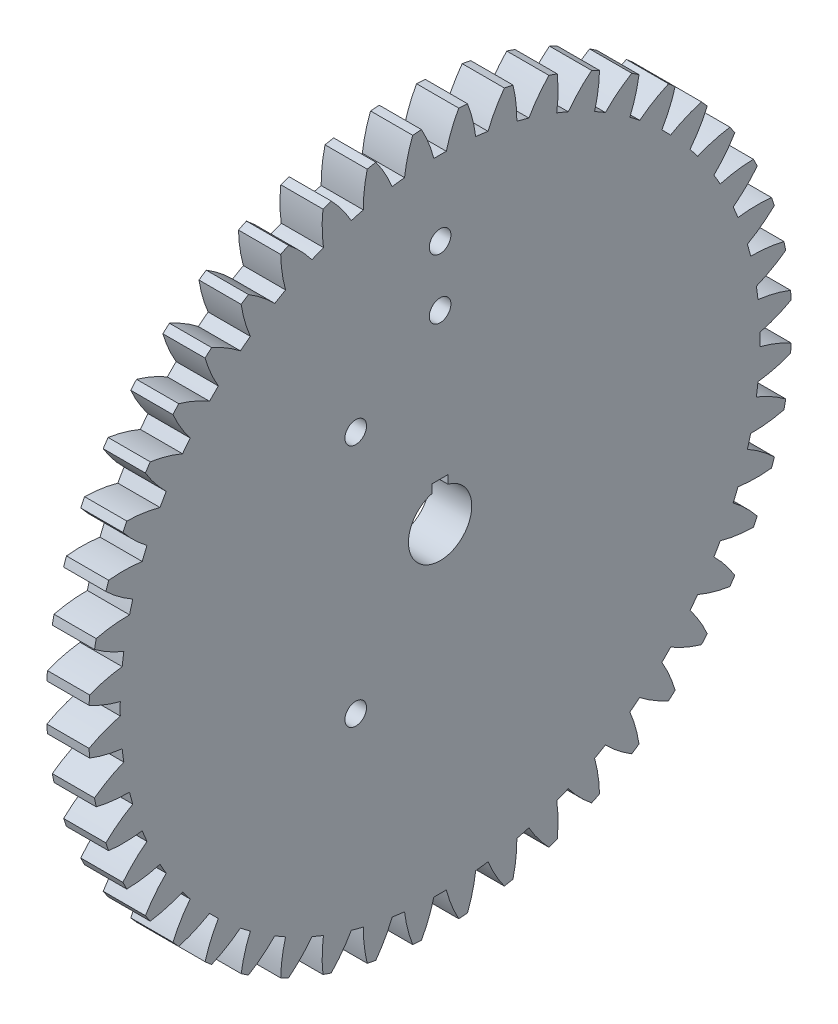
SolidWorks part; units mm, degrees
ref_plane "Plane1" through (0, 0, 0) normal (0, 0, 1) x (1, 0, 0)
ref_plane "Plane2" through (0, 0, 0) normal (0, 1, 0) x (1, 0, 0)
ref_plane "Plane3" through (0, 0, 0) normal (1, 0, 0) x (0, 0, -1)
other "Configuration Table"
sketch "HoldingSke" plane through (0, 0, 0) normal (0, 1, 0) x (1, 0, 0)
  line L0 (0, 0) -> (101.9755, -113.2553)
  line L1 (-15, 0) -> (100, 0) construction
  line L2 (0, 0) -> (-2.1039, 2.3779)
  line L3 (0, 0) -> (-11.863, 4.5341)
  line L4 (0, 0) -> (5.7786, 6.4178)
  line L5 (0, 0) -> (-47.5972, -17.7524)
  line L6 (0, 0) -> (-10.5278, -7.1032)
  line L7 (-2.1039, 2.3779) -> (8.8308, 51.9872)
  line L8 (-76.2, 54.61) -> (-54.9402, 54.61)
  line L9 (-71.009, 38.7566) -> (-53.1078, 45.2721)
  line L10 (-76.2, 71.12) -> (104.1128, 71.12)
  line L11 (0, 0) -> (-12.7, 0)
  line L12 (-76.2, 101.6) -> (-76.0298, 101.6)
  line L13 (24.9733, 27.94) -> (52.9518, 28.4284)
  line L14 (24.9733, 27.94) -> (24.9746, 27.94)
  line L15 (24.9733, 27.94) -> (100.4006, 29.5858)
  circle A0 centre (0, 0) radius 9.525
  circle A1 centre (0, 0) radius 38.1
  circle A2 centre (0, 0) radius 38.1
  circle A3 centre (0, 0) radius 9.525
  dimension "Num_teeth" = 48
  dimension "H" = 19.05
  dimension "Pitch_radius" = 180.3128
  dimension "Width" = 12.7
  dimension "Thickness" = 12.7
sketch "BasProSke" plane through (0, 0, 0) normal (0, 1, 0) x (1, 0, 0)
  line L0 (-10, 0) -> (60, 0) construction
  line L1 (0, 0) -> (0, 105.8333)
  line L2 (0, 0) -> (12.7, 0)
  line L3 (12.7, 0) -> (12.7, 105.8333)
  line L4 (12.7, 105.8333) -> (0, 105.8333)
  dimension "Thickness" = 12.7
  dimension "Diameter" = 211.6667
revolve "Base-Revolve" add sketch "BasProSke" angle 360 about L0
sketch "TooCutSke" plane through (0, 0, 0) normal (1, 0, 0) x (0, 0, -1)
  line L1 (0, 0) -> (0, 107) construction
  line L2 (0, 0) -> (-3.622, 101.5354) construction
  line L3 (0, 0) -> (-13.284, 202.675) construction
  line L4 (-3.622, 101.5354) -> (-6.642, 101.3375) construction
  arc A0 (1.8768, 96.2888) -> (-1.8768, 96.2888) centre (0, 0) ccw
  arc A1 (5.6186, 105.7095) -> (-5.6186, 105.7095) centre (0, 0) ccw
  circle A2 centre (0, 0) radius 101.6 construction
  circle A3 centre (0, 0) radius 95.4728 construction
  arc A4 (-1.8768, 96.2888) -> (-5.6186, 105.7095) centre (-41.2227, 86.1147) ccw
  arc A5 (5.6186, 105.7095) -> (1.8768, 96.2888) centre (41.2227, 86.1147) ccw
extrude "ToothCut" cut sketch "TooCutSke" along normal through all
fillet "Breaks" [suppressed] radius 0.0847 tangent propagation no
fillet "RootFillets" [suppressed] radius 1.0596
pattern_circular "TeethCuts" count 48 every 7.5 about axis through (-10, 0, 0) along (1, 0, 0) of "ToothCut", "RootFillets", "Breaks"
sketch "HubNeaOneSke" plane through (0, 0, 0) normal (-1, 0, 0) x (0, 0, 1)
  circle A0 centre (0, 0) radius 38.1
  dimension "Diameter" = 76.2
extrude "HubNearOne" [suppressed] add sketch "HubNeaOneSke" along normal blind 38.1001
sketch "HubNeaBotSke" plane through (0, 0, 0) normal (-1, 0, 0) x (0, 0, 1)
  circle A0 centre (0, 0) radius 38.1
  dimension "Diameter" = 76.2
extrude "HubNearBoth" [suppressed] add sketch "HubNeaBotSke" along normal blind 19.0501
ref_plane "FarPln" through (12.7, 0, 0) normal (1, 0, 0) x (0, 0, -1)
sketch "HubFarSke" plane through (12.7, 0, 0) normal (1, 0, 0) x (0, 0, -1)
  circle A0 centre (0, 0) radius 38.1
  dimension "Diameter" = 76.2
extrude "HubFar" [suppressed] add sketch "HubFarSke" along normal blind 19.0501
sketch "BorSke" plane through (0, 0, 0) normal (1, 0, 0) x (0, 0, -1)
  circle A0 centre (0, 0) radius 9.525
  dimension "Diameter" = 19.05
extrude "Bore" cut sketch "BorSke" along normal mid plane 101.6002
sketch "KeySke" plane through (0, 0, 0) normal (1, 0, 0) x (0, 0, -1)
  line L0 (-2.3813, 0) -> (-2.3813, 11.7348)
  line L1 (-2.3813, 11.7348) -> (2.3813, 11.7348)
  line L2 (2.3813, 11.7348) -> (2.3813, 0)
  line L3 (0, 0) -> (0, 34) construction
  line L4 (-2.3813, 0) -> (2.3813, 0)
  dimension "Width" = 4.7625
extrude "Keyway" cut sketch "KeySke" along normal mid plane 101.6002
pattern_circular "Keyway2" [suppressed] count 2 every 90 about axis through (-10, 0, 0) along (1, 0, 0)
sketch "Sketch1" plane through (0, 0, 0) normal (-1, 0, 0) x (0, 0, 1)
  line L0 (-32.7257, 64.77) -> (54.9532, 64.77) construction
  circle A0 centre (0, 73.7743) radius 3.2512
  circle A1 centre (0, 55.7657) radius 3.2512
  dimension "D1" = 6.5024
  dimension "D2" = 18.0086
  dimension "D3" = 64.77
extrude "Cut-Extrude1" cut sketch "Sketch1" against normal through all
sketch "Sketch2" plane through (0, 0, 0) normal (-1, 0, 0) x (0, 0, 1)
  line L0 (41.1124, 0) -> (-29.3128, 0) construction
  circle A0 centre (25.4, -36.703) radius 3.2512
  circle A1 centre (25.4, 36.703) radius 3.2512
  dimension "D2" = 6.5024
  dimension "D1" = 73.406
  dimension "D3" = 25.4
extrude "Cut-Extrude2" cut sketch "Sketch2" against normal through all
equation "' \"Pitch@HoldingSke\" = 4"
equation "' \"Num_teeth@HoldingSke\" = 12"
equation "' \"Ap@HoldingSke\" =  20"
equation "' \"Ap@HoldingSke\" = 20"
equation "' \"Width@HoldingSke\" = 0.5"
equation "' \"Hub_dia@HoldingSke\"= 1"
equation "' \"Hub_dia@HoldingSke\" = 1"
equation "' \"Overall_len@HoldingSke\" = 1.0"
equation "' \"Bore@HoldingSke\" = 0.75"
equation "' \"T_dim@HoldingSke\" = 0.85"
equation "' \"Width@KeySke\" = 0.25"
equation "' \"Show_teeth@HoldingSke\" = 13"
equation "' \"Backlash@HoldingSke\" = 0.009"
equation "' \"Addendum_fac@HoldingSke\" = 1.0"
equation "' \"Dedendum_fac@HoldingSke\" = 1.25"
equation "' \"Dedendum_add@HoldingSke\" = 0.00005"
equation "' \"Clearance_fac@HoldingSke\" = 0.25"
equation "' \"Pitch@HoldingSke\" = 0.5"
equation "' \"Num_teeth@HoldingSke\" = 23"
equation "' \"Show_teeth@HoldingSke\" = 23"
equation "' \"Backlash@HoldingSke\" = 0.0375"
equation "\"Overcut_dia@TooCutSke\" = (\"Num_teeth@HoldingSke\" + 2 * \"Addendum_fac@HoldingSke\") / \"Pitch@HoldingSke\" + 0.002"
equation "\"Pitch_dia@TooCutSke\" = \"Num_teeth@HoldingSke\" / \"Pitch@HoldingSke\""
equation "\"Base_dia@TooCutSke\" = \"Num_teeth@HoldingSke\" / \"Pitch@HoldingSke\" * cos((\"Ap@HoldingSke\"  * 3.14159265 / 180))"
equation "\"Root_dia@TooCutSke\" = (\"Num_teeth@HoldingSke\" + 2) / \"Pitch@HoldingSke\" - 2 * (\"Addendum_fac@HoldingSke\" + \"Dedendum_fac@HoldingSke\") / \"Pitch@HoldingSke\" - \"Dedendum_add@HoldingSke\" * 2"
equation "\"Half_ang@TooCutSke\" = 180 / \"Num_teeth@HoldingSke\""
equation "\"Half_CT@TooCutSke\" = \"Num_teeth@HoldingSke\" / \"Pitch@HoldingSke\" * sin((3.14159265 / 2 / \"Num_teeth@HoldingSke\")) / 2 - 7 * \"Backlash@HoldingSke\" / 4"
equation "\"Flank_rad@TooCutSke\" = \"Num_teeth@HoldingSke\" / \"Pitch@HoldingSke\" / 5"
equation "\"Radius@RootFillets\" = \"Clearance_fac@HoldingSke\" / \"Pitch@HoldingSke\" + \"Dedendum_add@HoldingSke\""
equation "\"Break_rad@Breaks\" = 0.02 / \"Pitch@HoldingSke\""
equation "\"Thickness@HoldingSke\" = \"Width@HoldingSke\""
equation "\"OAL@HoldingSke\" = \"Thickness@HoldingSke\""
equation "\"MHD@HoldingSke\" = (\"Num_teeth@HoldingSke\" + 2) / \"Pitch@HoldingSke\" - 2 * (\"Addendum_fac@HoldingSke\" + \"Dedendum_fac@HoldingSke\")  / \"Pitch@HoldingSke\" - \"Dedendum_add@HoldingSke\" * 2"
equation "\"MBD@HoldingSke\" = (\"Num_teeth@HoldingSke\" + 2) / \"Pitch@HoldingSke\" - 2 * (\"Addendum_fac@HoldingSke\" + \"Dedendum_fac@HoldingSke\")  / \"Pitch@HoldingSke\" - \"Dedendum_add@HoldingSke\" * 2 - 0.002"
equation "\"MHD@HoldingSke\" = ((sgn( \"MHD@HoldingSke\" - \"Hub_dia@HoldingSke\" )-1)*( \"MHD@HoldingSke\" - \"Hub_dia@HoldingSke\" ))/-2+ \"Hub_dia@HoldingSke\""
equation "\"MBD@HoldingSke\" = ((sgn( \"MBD@HoldingSke\" - \"Bore@HoldingSke\" )-1)*( \"MBD@HoldingSke\" - \"Bore@HoldingSke\" ))/-2+ \"Bore@HoldingSke\""
equation "\"OAL@HoldingSke\" = ((sgn( \"OAL@HoldingSke\" - \"Overall_len@HoldingSke\" )+1)*( \"OAL@HoldingSke\" - \"Overall_len@HoldingSke\" ))/2 + \"Overall_len@HoldingSke\" + 0.000002"
equation "\"Num_teeth@TeethCuts\" = int( \"Show_teeth@HoldingSke\" ) + 1"
equation "\"Num_teeth@TeethCuts\" = ((sgn( \"Num_teeth@TeethCuts\" - \"Num_teeth@HoldingSke\" )-1)*( \"Num_teeth@TeethCuts\" - \"Num_teeth@HoldingSke\" ))/-2+ \"Num_teeth@HoldingSke\""
equation "\"Num_teeth@TeethCuts\" = ((sgn( \"Num_teeth@TeethCuts\" - 2.0)+1)*( \"Num_teeth@TeethCuts\" - 2.0))/2 +2.0"
equation "\"Angle@TeethCuts\" = 360.0 / \"Num_teeth@HoldingSke\""
equation "\"Diameter@BasProSke\" = (\"Num_teeth@HoldingSke\" + 2 * \"Addendum_fac@HoldingSke\") / \"Pitch@HoldingSke\""
equation "\"Thickness@BasProSke\"  = \"Thickness@HoldingSke\""
equation "' \"Fillet_rad@BasProSke\" =  \"Thickness@HoldingSke\" * 0.05"
equation "' \"Fillet_rad@BasProSke\" = \"Thickness@HoldingSke\" * 0.05"
equation "\"MHD@HoldingSke\" = ((sgn( \"MHD@HoldingSke\" - \"Root_dia@TooCutSke\" )-1)*( \"MHD@HoldingSke\" - \"Root_dia@TooCutSke\" ))/-2+ \"Root_dia@TooCutSke\""
equation "\"Diameter@HubNeaOneSke\" = \"MHD@HoldingSke\""
equation "\"Length@HubNearOne\" = \"OAL@HoldingSke\" - \"Thickness@BasProSke\""
equation "\"Diameter@HubNeaBotSke\" = \"MHD@HoldingSke\""
equation "\"Length@HubNearBoth\" = ( \"OAL@HoldingSke\" - \"Thickness@BasProSke\" ) / 2.0"
equation "\"Thickness@FarPln\" = \"Thickness@BasProSke\""
equation "\"Diameter@HubFarSke\" = \"MHD@HoldingSke\""
equation "\"Length@HubFar\" = ( \"OAL@HoldingSke\" - \"Thickness@BasProSke\" ) / 2.0"
equation "\"Diameter@BorSke\" = \"MBD@HoldingSke\""
equation "\"D1@Bore\" = \"OAL@HoldingSke\" * 2.0"
equation "\"D1@Keyway\" = \"OAL@HoldingSke\" * 2.0"
equation "\"Offset@KeySke\" = \"T_dim@HoldingSke\" - \"MBD@HoldingSke\" / 2.0"
